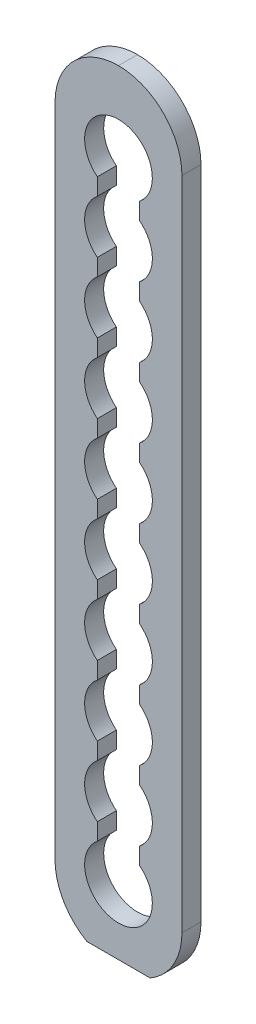
SolidWorks part; units mm, degrees
ref_plane "Alzado" through (0, 0, 0) normal (0, 0, 1) x (1, 0, 0)
ref_plane "Planta" through (0, 0, 0) normal (0, 1, 0) x (1, 0, 0)
ref_plane "Vista lateral" through (0, 0, 0) normal (1, 0, 0) x (0, 0, -1)
sketch "Croquis1" plane through (0, 0, 0) normal (0, 0, 1) x (1, 0, 0)
  line L0 (0, -72.5) -> (0, 72.5) construction
  line L1 (-15, 92.5) -> (15, 92.5)
  line L2 (-15, 92.5) -> (-15, -92.5)
  line L3 (-15, -92.5) -> (15, -92.5)
  line L4 (15, 92.5) -> (15, -92.5)
  line L33 (0, 72.5) -> (0, -72.5) construction
  line L34 (5, 72.5) -> (5, -72.5)
  line L35 (-5, 72.5) -> (-5, -72.5)
  arc A28 (5, 72.5) -> (-5, 72.5) centre (0, 72.5) ccw
  arc A29 (-5, -72.5) -> (5, -72.5) centre (0, -72.5) ccw
  point P4 (-15, 0)
  point P5 (0, 92.5)
  point P8 (0, 0)
  dimension "D5" = 145
  dimension "D2" = 5
  dimension "D1" = 30
  dimension "D3" = 20
  dimension "D4" = 20
  dimension "D8" = 15
extrude "Saliente-Extruir1" add sketch "Croquis1" along normal blind 4.5
fillet "Redondeo1" radius 15 4 edges at (15, -92.5, 2.25) (-15, -92.5, 2.25) (-15, 92.5, 2.25) (15, 92.5, 2.25)
sketch "Croquis2" plane through (0, 0, 4.5) normal (0, 0, 1) x (1, 0, 0)
  circle A0 centre (0, 73.5) radius 8
  circle A13 centre (0, 57) radius 8
  circle A14 centre (0, 40.5) radius 8
  circle A15 centre (0, 24) radius 8
  circle A16 centre (0, 7.5) radius 8
  circle A17 centre (0, -9) radius 8
  circle A18 centre (0, -25.5) radius 8
  circle A29 centre (0, -42) radius 8
  circle A30 centre (0, -58.5) radius 8
  circle A31 centre (0, -75) radius 8
  dimension "D1" = 16
  dimension "D2" = 19
  dimension "D3" = 10
extrude "Cortar-Extruir1" cut sketch "Croquis2" against normal blind 10
sketch "Croquis3" plane through (0, 0, 4.5) normal (0, 0, 1) x (1, 0, 0)
  line L0 (0, -92.5) -> (13.3818, -92.5) construction
  line L1 (-17.8715, -90.5) -> (18.2039, -90.5)
  line L2 (-17.8715, -90.5) -> (-17.8715, -102.0596)
  line L3 (-17.8715, -102.0596) -> (18.2039, -102.0596)
  line L4 (18.2039, -90.5) -> (18.2039, -102.0596)
  dimension "D1" = 2
extrude "Cortar-Extruir2" cut sketch "Croquis3" against normal blind 10
